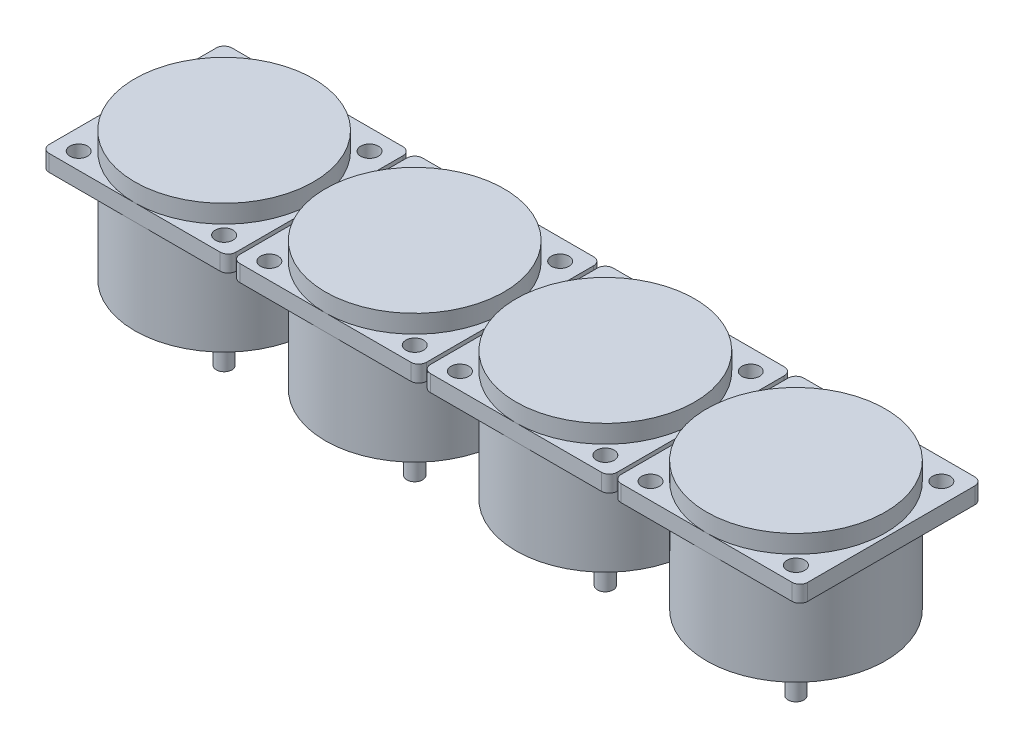
SolidWorks part; units mm, degrees
ref_plane "Front Plane" through (0, 0, 0) normal (0, 0, 1) x (1, 0, 0)
ref_plane "Top Plane" through (0, 0, 0) normal (0, 1, 0) x (1, 0, 0)
ref_plane "Right Plane" through (0, 0, 0) normal (1, 0, 0) x (0, 0, -1)
sketch "Dial Face" plane through (0, 0, 0) normal (0, 1, 0) x (1, 0, 0)
  line L1 (21.75, 23.75) -> (-21.75, 23.75)
  line L2 (23.75, 21.75) -> (23.75, -20.75)
  line L3 (21.75, -22.75) -> (-21.75, -22.75)
  line L4 (-23.75, 21.75) -> (-23.75, -20.75)
  line L5 (24.75, 21.75) -> (24.75, -20.75)
  line L6 (72.25, 21.75) -> (72.25, -20.75)
  line L7 (70.25, -22.75) -> (26.75, -22.75)
  line L8 (70.25, 23.75) -> (26.75, 23.75)
  line L9 (73.25, 21.75) -> (73.25, -20.75)
  line L10 (120.75, 21.75) -> (120.75, -20.75)
  line L11 (118.75, -22.75) -> (75.25, -22.75)
  line L12 (118.75, 23.75) -> (75.25, 23.75)
  line L13 (121.75, 21.75) -> (121.75, -20.75)
  line L14 (169.25, 21.75) -> (169.25, -20.75)
  line L15 (167.25, -22.75) -> (123.75, -22.75)
  line L16 (167.25, 23.75) -> (123.75, 23.75)
  circle A0 centre (0, 0) radius 22.75
  circle A1 centre (18.5, 18.5) radius 2.25
  circle A2 centre (18.5, -18.5) radius 2.25
  circle A3 centre (-18.5, 18.5) radius 2.25
  circle A4 centre (-18.5, -18.5) radius 2.25
  arc A5 (21.75, 23.75) -> (23.75, 21.75) centre (21.75, 21.75) cw
  arc A6 (23.75, -20.75) -> (21.75, -22.75) centre (21.75, -20.75) cw
  arc A7 (-21.75, -22.75) -> (-23.75, -20.75) centre (-21.75, -20.75) cw
  arc A8 (-21.75, 23.75) -> (-23.75, 21.75) centre (-21.75, 21.75) ccw
  arc A9 (70.25, 23.75) -> (72.25, 21.75) centre (70.25, 21.75) cw
  arc A10 (26.75, 23.75) -> (24.75, 21.75) centre (26.75, 21.75) ccw
  circle A11 centre (67, -18.5) radius 2.25
  circle A12 centre (67, 18.5) radius 2.25
  circle A13 centre (30, 18.5) radius 2.25
  circle A14 centre (30, -18.5) radius 2.25
  arc A15 (26.75, -22.75) -> (24.75, -20.75) centre (26.75, -20.75) cw
  circle A16 centre (48.5, 0) radius 22.75
  arc A17 (72.25, -20.75) -> (70.25, -22.75) centre (70.25, -20.75) cw
  arc A18 (118.75, 23.75) -> (120.75, 21.75) centre (118.75, 21.75) cw
  arc A19 (75.25, 23.75) -> (73.25, 21.75) centre (75.25, 21.75) ccw
  circle A20 centre (115.5, -18.5) radius 2.25
  circle A21 centre (115.5, 18.5) radius 2.25
  circle A22 centre (78.5, 18.5) radius 2.25
  circle A23 centre (78.5, -18.5) radius 2.25
  arc A24 (75.25, -22.75) -> (73.25, -20.75) centre (75.25, -20.75) cw
  circle A25 centre (97, 0) radius 22.75
  arc A26 (120.75, -20.75) -> (118.75, -22.75) centre (118.75, -20.75) cw
  arc A27 (167.25, 23.75) -> (169.25, 21.75) centre (167.25, 21.75) cw
  arc A28 (123.75, 23.75) -> (121.75, 21.75) centre (123.75, 21.75) ccw
  circle A29 centre (164, -18.5) radius 2.25
  circle A30 centre (164, 18.5) radius 2.25
  circle A31 centre (127, 18.5) radius 2.25
  circle A32 centre (127, -18.5) radius 2.25
  arc A33 (123.75, -22.75) -> (121.75, -20.75) centre (123.75, -20.75) cw
  circle A34 centre (145.5, 0) radius 22.75
  arc A35 (169.25, -20.75) -> (167.25, -22.75) centre (167.25, -20.75) cw
  circle A36 centre (-10, -10) radius 2
  circle A37 centre (10, -10) radius 2.0018
  circle A38 centre (38.5, -10) radius 2
  circle A39 centre (58.5, -10) radius 2.0018
  circle A40 centre (87, -10) radius 2
  circle A41 centre (107, -10) radius 2.0018
  circle A42 centre (135.5, -10) radius 2
  circle A43 centre (155.5, -10) radius 2.0018
extrude "Boss-Extrude11" add sketch "Dial Face" along normal blind 8.8 contours A0 | A16 | A25 | A34
extrude "Boss-Extrude12" add sketch "Dial Face<16>" along normal blind 4.2 contours A8 L4 A7 L3 A6 L2 A5 L1 | A10 L5 A15 L7 A17 L6 A9 L8 | A19 L9 A24 L11 A26 L10 A18 L12 | A33 L13 A28 L16 A27 L14 A35 L15
sketch "Dial Face<16>" plane through (0, 0, 0) normal (0, 1, 0) x (1, 0, 0) same geometry as "Dial Face"
extrude "Cut-Extrude9" cut sketch "Dial Face<17>" along normal up to next contours A1 | A2 | A3 | A4 | A12 | A11 | A14 | A13 | A21 | A20 | A23 | A22 | A30 | A29 | A32 | A31
sketch "Dial Face<17>" plane through (0, 0, 0) normal (0, 1, 0) x (1, 0, 0) same geometry as "Dial Face"
extrude "Boss-Extrude13" add sketch "Dial Face<19>" against normal blind 24 contours A0 | A16 | A25 | A34
sketch "Dial Face<19>" plane through (0, 0, 0) normal (0, 1, 0) x (1, 0, 0) same geometry as "Dial Face"
extrude "Boss-Extrude14" add sketch "Dial Face<21>" against normal blind 33 contours A36 | A37 | A38 | A39 | A40 | A41 | A42 | A43
sketch "Dial Face<21>" plane through (0, 0, 0) normal (0, 1, 0) x (1, 0, 0) same geometry as "Dial Face"
